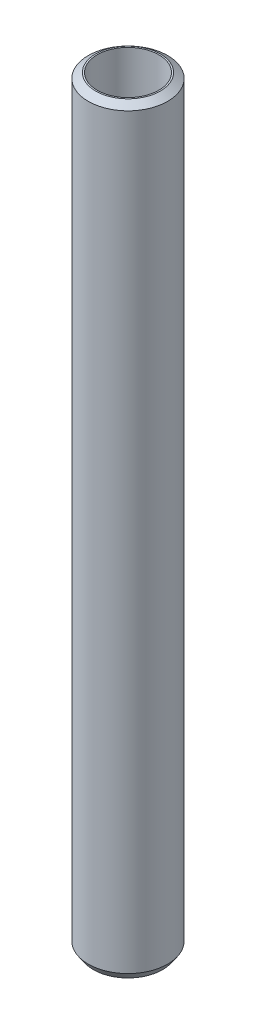
SolidWorks part; units mm, degrees
ref_plane "Front Plane" through (0, 0, 0) normal (0, 0, 1) x (1, 0, 0)
ref_plane "Top Plane" through (0, 0, 0) normal (0, 1, 0) x (1, 0, 0)
ref_plane "Right Plane" through (0, 0, 0) normal (1, 0, 0) x (0, 0, -1)
sketch "Sketch1" plane through (0, 0, 0) normal (0, 1, 0) x (1, 0, 0)
  circle A0 centre (0, 0) radius 30
  dimension "SHAFT_OD" = 60
extrude "Boss-Extrude1" add sketch "Sketch1" along normal blind 573.7961
sketch "Sketch2" plane through (0, 0, 0) normal (0, 1, 0) x (1, 0, 0)
  circle A0 centre (0, 0) radius 23.2501
  dimension "BORE_D" = 46.5001
extrude "Cut-Extrude1" cut sketch "Sketch2" along normal through all
chamfer "Chamfer1" distance 3.884 angle 55.388 2 edges at (0, 573.7961, 30) (0, 0, 30) first distance on face at (0, 573.7961, 30) first distance on face at (0, 0, 23.2501)
